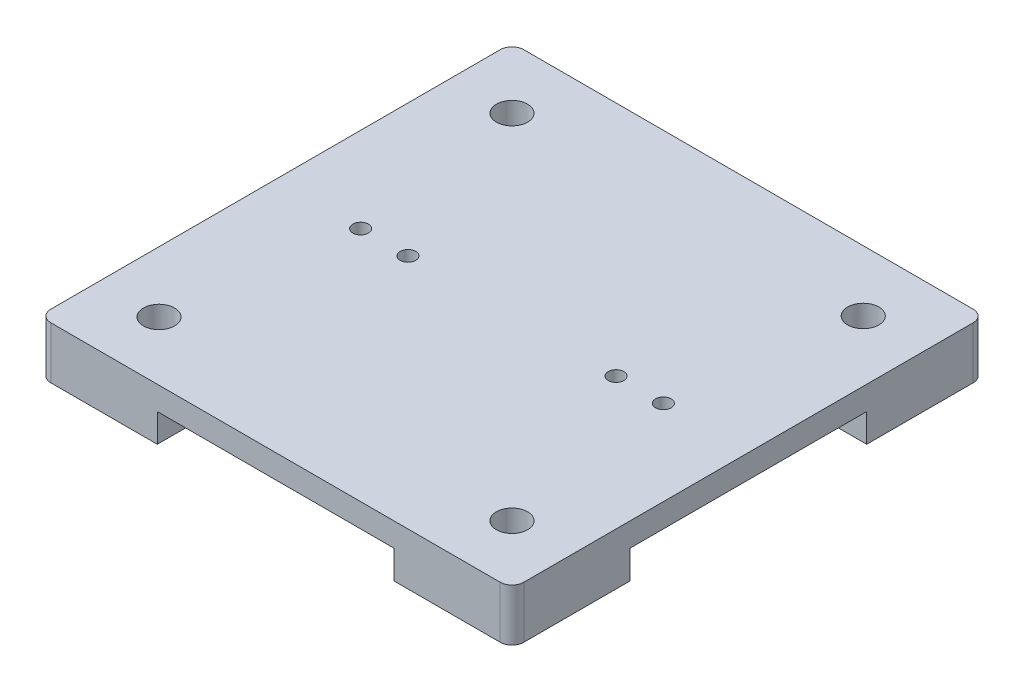
SolidWorks part; units mm, degrees
ref_plane "Front Plane" through (0, 0, 0) normal (0, 0, 1) x (1, 0, 0)
ref_plane "Top Plane" through (0, 0, 0) normal (0, 1, 0) x (1, 0, 0)
ref_plane "Right Plane" through (0, 0, 0) normal (1, 0, 0) x (0, 0, -1)
sketch "Sketch1" plane through (0, 0, 0) normal (0, 1, 0) x (1, 0, 0)
  line L0 (-37.5, 6.35) -> (37.5, 6.35) construction
  line L1 (-37.5, 6.35) -> (-37.5, -6.35)
  line L2 (-37.5, -6.35) -> (37.5, -6.35)
  line L3 (37.5, 6.35) -> (37.5, -6.35)
  line L4 (-37.5, 6.35) -> (37.5, -6.35) construction
  line L5 (-37.5, -6.35) -> (37.5, 6.35) construction
  line L6 (0, 6.35) -> (0, -6.35) construction
  line L7 (-37.5, 0) -> (37.5, 0) construction
  line L9 (-47.5, 50) -> (47.5, 50)
  line L10 (-50, 47.5) -> (-50, -47.5)
  line L11 (-47.5, -50) -> (47.5, -50)
  line L12 (50, 47.5) -> (50, -47.5)
  line L13 (-50, 50) -> (50, -50) construction
  line L14 (-50, -50) -> (50, 50) construction
  circle A0 centre (-32, 0) radius 1.65
  circle A1 centre (-22, 0) radius 1.65
  circle A2 centre (22, 0) radius 1.65
  circle A3 centre (32, 0) radius 1.65
  circle A4 centre (-32, 0) radius 1.625
  circle A5 centre (-22, 0) radius 1.625
  circle A6 centre (22, 0) radius 1.625
  circle A7 centre (32, 0) radius 1.625
  arc A8 (-50, 47.5) -> (-47.5, 50) centre (-47.5, 47.5) cw
  arc A9 (-50, -47.5) -> (-47.5, -50) centre (-47.5, -47.5) ccw
  arc A10 (47.5, -50) -> (50, -47.5) centre (47.5, -47.5) ccw
  arc A11 (50, 47.5) -> (47.5, 50) centre (47.5, 47.5) ccw
  point P0 (0, 0)
  point P5 (0, 0)
  point P24 (0, 0)
  dimension "D7" = 3.3
  dimension "D8" = 3.25
  dimension "D11" = 2.5
  dimension "D12" = 2.5
  dimension "D1" = 75
  dimension "D2" = 12.7
  dimension "D3" = 5.5
  dimension "D4" = 15.5
  dimension "D5" = 5.5
  dimension "D6" = 15.5
  dimension "D9" = 100
  dimension "D10" = 100
extrude "Boss-Extrude1" add sketch "Sketch1" along normal blind 5 contours A9 L11 A10 L12 A11 L9 A8 L10
sketch "Sketch2" plane through (0, 0, 0) normal (0, -1, 0) x (1, 0, 0)
  line L1 (-50, -47.5) -> (-50, 47.5) construction
  line L2 (-25, 25) -> (-50, 25)
  line L3 (-25, 25) -> (-25, 50)
  line L4 (-50, 47.5) -> (-50, -47.5)
  line L5 (-47.5, -50) -> (47.5, -50)
  line L6 (50, -47.5) -> (50, 47.5)
  line L7 (47.5, 50) -> (-47.5, 50)
  line L12 (-25, 50) -> (-47.5, 50)
  line L13 (-50, 25) -> (-50, 47.5)
  line L14 (-25, 25) -> (-49.2678, 49.2678) construction
  line L15 (-25, 50) -> (-50, 25) construction
  line L16 (25, 25) -> (50, 25)
  line L17 (25, 25) -> (25, 50)
  line L18 (25, 50) -> (47.5, 50)
  line L19 (50, 25) -> (50, 47.5)
  line L20 (25, 25) -> (49.2678, 49.2678) construction
  line L21 (25, 50) -> (50, 25) construction
  line L22 (25, -25) -> (50, -25)
  line L23 (25, -25) -> (25, -50)
  line L24 (25, -50) -> (47.5, -50)
  line L25 (50, -25) -> (50, -47.5)
  line L26 (25, -25) -> (49.2678, -49.2678) construction
  line L27 (25, -50) -> (50, -25) construction
  line L28 (-25, -25) -> (-50, -25)
  line L29 (-25, -25) -> (-25, -50)
  line L30 (-25, -50) -> (-47.5, -50)
  line L31 (-50, -25) -> (-50, -47.5)
  line L32 (-25, -25) -> (-49.2678, -49.2678) construction
  line L33 (-25, -50) -> (-50, -25) construction
  line L34 (-47.5, 50) -> (47.5, 50) construction
  line L35 (50, -47.5) -> (50, 47.5) construction
  line L36 (-47.5, -50) -> (47.5, -50) construction
  arc A0 (-50, -47.5) -> (-47.5, -50) centre (-47.5, -47.5) ccw construction
  arc A1 (47.5, -50) -> (50, -47.5) centre (47.5, -47.5) ccw construction
  arc A2 (50, 47.5) -> (47.5, 50) centre (47.5, 47.5) ccw construction
  arc A3 (-47.5, 50) -> (-50, 47.5) centre (-47.5, 47.5) ccw construction
  arc A4 (-50, -47.5) -> (-47.5, -50) centre (-47.5, -47.5) ccw
  arc A5 (47.5, -50) -> (50, -47.5) centre (47.5, -47.5) ccw
  arc A6 (50, 47.5) -> (47.5, 50) centre (47.5, 47.5) ccw
  arc A7 (-47.5, 50) -> (-50, 47.5) centre (-47.5, 47.5) ccw
  arc A8 (-50, -47.5) -> (-47.5, -50) centre (-47.5, -47.5) ccw
  arc A9 (47.5, -50) -> (50, -47.5) centre (47.5, -47.5) ccw
  arc A10 (50, 47.5) -> (47.5, 50) centre (47.5, 47.5) ccw
  arc A11 (-47.5, 50) -> (-50, 47.5) centre (-47.5, 47.5) ccw
  point P2 (37.5, 37.5)
  point P9 (-37.5, 37.5)
  point P22 (37.5, -37.5)
  point P27 (-37.5, -37.5)
  dimension "D2" = 25
  dimension "D3" = 25
  dimension "D4" = 25
  dimension "D5" = 25
  dimension "D1" = 0
extrude "Boss-Extrude2" add sketch "Sketch2" along normal blind 6
sketch "Sketch5" plane through (0, 5, 0) normal (0, 1, 0) x (1, 0, 0)
  line L0 (-25, 25) -> (-49.2678, 49.2678) construction
  line L1 (-37.1339, 37.1339) -> (37.5, 37.1339)
  line L2 (-37.1339, 37.1339) -> (-37.1339, -37.5)
  line L3 (-37.1339, -37.5) -> (37.5, -37.5)
  line L4 (37.5, 37.1339) -> (37.5, -37.5)
  line L5 (25, 25) -> (49.2678, 49.2678) construction
  point P0 (-37.1339, 37.1339)
  point P1 (37.5, -37.5)
  point P2 (-37.1339, -37.5)
  point P15 (37.1339, 37.1339)
extrude "Cut-Extrude1" cut sketch "Sketch1<3>" along normal through all contours A0 | A1 | A2 | A3
sketch "Sketch1<3>" plane through (0, 0, 0) normal (0, 1, 0) x (1, 0, 0) same geometry as "Sketch1"
hole_wizard "M6 Clearance Hole2" positions "Sketch5" profile "Sketch8" hole size "M6" standard "ISO" end condition through all
sketch "Sketch8" plane through (-37.1339, 5, -37.1339) normal (1, 0, 0) x (0, 0, 1)
  line L0 (0, 0) -> (0, 11)
  line L1 (0, 11) -> (3.3, 11)
  line L2 (3.3, 11) -> (3.3, 0)
  line L5 (3.3, 0) -> (0, 0)
  line L11 (0, -6.35) -> (0, 107.95) construction
  dimension "Thru Hole Dia." = 6.6
  dimension "Thru Hole Depth" = 11
